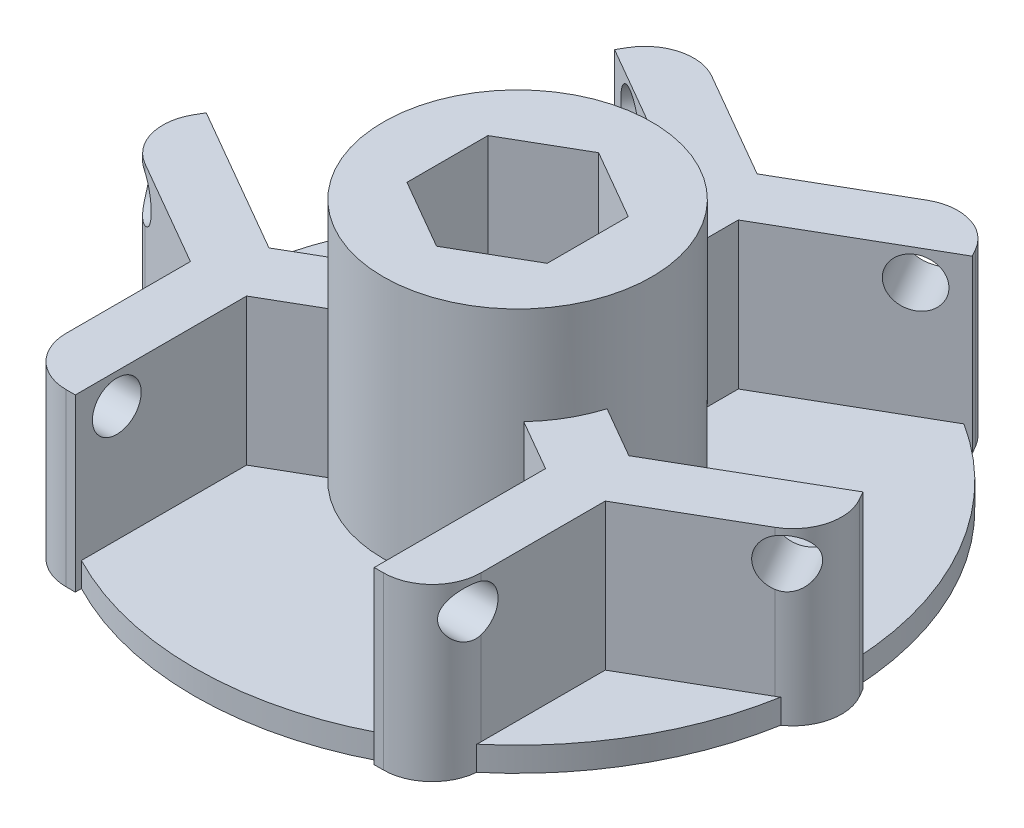
SolidWorks part; units mm, degrees
ref_plane "Alzado" through (0, 0, 0) normal (0, 0, 1) x (1, 0, 0)
ref_plane "Planta" through (0, 0, 0) normal (0, 1, 0) x (1, 0, 0)
ref_plane "Vista lateral" through (0, 0, 0) normal (1, 0, 0) x (0, 0, -1)
sketch "Croquis2" plane through (0, 0, 0) normal (0, 1, 0) x (1, 0, 0)
  circle A0 centre (0, 0) radius 26.5
  dimension "D1" = 53
extrude "Saliente-Extruir1" add sketch "Croquis2" along normal blind 2 and the other way blind 2
sketch "Croquis3" plane through (0, 0, 0) normal (0, 1, 0) x (1, 0, 0)
  line L1 (0, 6.6395) -> (-5.75, 3.3198)
  line L2 (-5.75, 3.3198) -> (-5.75, -3.3198)
  line L3 (-5.75, -3.3198) -> (0, -6.6395)
  line L4 (0, -6.6395) -> (5.75, -3.3198)
  line L5 (5.75, -3.3198) -> (5.75, 3.3198)
  line L6 (5.75, 3.3198) -> (0, 6.6395)
  circle A0 centre (0, 0) radius 11
  circle A1 centre (0, 0) radius 5.75 construction
  dimension "D1" = 22
  dimension "D2" = 11.5
extrude "Saliente-Extruir2" add sketch "Croquis3" along normal blind 22 and the other way blind 22
sketch "Croquis5" plane through (0, 0, 0) normal (0, 1, 0) x (1, 0, 0)
  line L0 (0, 0) -> (0, 3)
  line L2 (0, 0) -> (16.4545, -9.5)
  line L3 (0, 0) -> (-16.4545, -9.5)
  line L4 (-2.5, 8.395) -> (2.5, 8.395)
  line L6 (-2.5, 8.395) -> (-2.5, 19)
  line L7 (-2.5, 19) -> (2.5, 19)
  line L8 (2.5, 8.395) -> (2.5, 19)
  line L9 (8.5203, -2.0324) -> (17.7045, -7.3349)
  line L10 (17.7045, -7.3349) -> (15.2045, -11.6651)
  line L11 (6.0203, -6.3625) -> (15.2045, -11.6651)
  line L12 (8.5203, -2.0324) -> (6.0203, -6.3625)
  line L13 (-6.0203, -6.3625) -> (-15.2045, -11.6651)
  line L14 (-15.2045, -11.6651) -> (-17.7045, -7.3349)
  line L15 (-8.5203, -2.0324) -> (-17.7045, -7.3349)
  line L16 (-6.0203, -6.3625) -> (-8.5203, -2.0324)
  circle A0 centre (0, 0) radius 11 construction
  point P5 (0, 11)
  point P23 (0, 0)
  dimension "D1" = 120
  dimension "D2" = 120
  dimension "D3" = 19
  dimension "D4" = 19
  dimension "D5" = 3
  dimension "D6" = 5
extrude "Saliente-Extruir3" add sketch "Croquis5" along normal blind 14 contours L11 L10 L9 L12 | L13 L14 L15 L16 | L6 L7 L8 L4
sketch "Croquis6" plane through (0, 0, 0) normal (0, 1, 0) x (1, 0, 0)
  line L0 (0, -24.2) -> (0, 24.2) construction
  line L2 (-12.25, -11) -> (-12.25, -24)
  line L4 (12.25, -11) -> (12.25, -24)
  line L5 (12.25, -24) -> (13, -24)
  line L6 (-1.6692, 15.1088) -> (0.7058, 19.2224)
  line L7 (12.25, -23.4987) -> (12.25, -17.4531)
  line L8 (-12.25, -11) -> (-12.25, -9)
  line L9 (-13, -24) -> (-12.25, -24)
  line L10 (-17, -20) -> (-17, -9)
  line L12 (17, -20) -> (17, -9)
  line L13 (-12.25, -9) -> (-17, -9)
  line L14 (12.25, -11) -> (12.25, -9)
  line L15 (12.25, -9) -> (17, -9)
  line L16 (-8.8205, 24.7224) -> (0.7058, 19.2224)
  line L17 (-14.2846, 23.2583) -> (-14.6596, 22.6088)
  line L18 (-3.4013, 16.1088) -> (-14.6596, 22.6088)
  line L19 (-3.4013, 16.1088) -> (-1.6692, 15.1088)
  line L20 (-15.6513, -5.1088) -> (-26.9096, 1.3912)
  line L21 (-26.9096, 1.3912) -> (-27.2846, 0.7417)
  line L22 (-25.8205, -4.7224) -> (-16.2942, -10.2224)
  line L23 (-13.9192, -6.1088) -> (-16.2942, -10.2224)
  line L24 (-15.6513, -5.1088) -> (-13.9192, -6.1088)
  line L25 (13.9192, -6.1088) -> (16.2942, -10.2224)
  line L26 (25.8205, -4.7224) -> (16.2942, -10.2224)
  line L27 (27.2846, 0.7417) -> (26.9096, 1.3912)
  line L28 (15.6513, -5.1088) -> (26.9096, 1.3912)
  line L29 (15.6513, -5.1088) -> (13.9192, -6.1088)
  line L30 (3.4013, 16.1088) -> (14.6596, 22.6088)
  line L31 (14.6596, 22.6088) -> (14.2846, 23.2583)
  line L32 (8.8205, 24.7224) -> (-0.7058, 19.2224)
  line L33 (1.6692, 15.1088) -> (-0.7058, 19.2224)
  line L34 (3.4013, 16.1088) -> (1.6692, 15.1088)
  arc A0 (-14.2846, 23.2583) -> (-8.8205, 24.7224) centre (-10.8205, 21.2583) cw
  arc A1 (-27.2846, 0.7417) -> (-25.8205, -4.7224) centre (-23.8205, -1.2583) ccw
  circle A2 centre (0, 0) radius 26.5 construction
  arc A3 (13, -24) -> (17, -20) centre (13, -20) ccw
  arc A4 (-13, -24) -> (-17, -20) centre (-13, -20) cw
  arc A5 (27.2846, 0.7417) -> (25.8205, -4.7224) centre (23.8205, -1.2583) cw
  arc A6 (14.2846, 23.2583) -> (8.8205, 24.7224) centre (10.8205, 21.2583) ccw
  point P21 (17, -24)
  point P24 (-17, -24)
  point P53 (0, 0)
  dimension "D9" = 4
  dimension "D1" = 24.5
  dimension "D2" = 3
  dimension "D3" = 12.25
  dimension "D5" = 34
  dimension "D6" = 17
extrude "Saliente-Extruir5" add sketch "Croquis6" along normal blind 14 contours L2 L9 A4 L10 L13 L8 | L4 L5 A3 L12 L15 L14 | L20 L21 A1 L22 L23 L24 | L6 L16 A0 L17 L18 L19 | L30 L31 A6 L32 L33 L34 | L25 L26 A5 L27 L28 L29
sketch "Croquis7" plane through (0, 0, 0) normal (0, 1, 0) x (1, 0, 0)
  line L0 (12.25, -23.4987) -> (12.25, -9.9593) construction
  line L1 (-12.25, -30.1) -> (12.25, -30.1)
  line L2 (-12.25, -30.1) -> (-12.25, -11.1)
  line L3 (-12.25, -11.1) -> (12.25, -11.1)
  line L4 (12.25, -30.1) -> (12.25, -11.1)
  line L5 (-24.2, 0) -> (24.2, 0) construction
  dimension "D1" = 19
  dimension "D2" = 30.1
  dimension "D3" = 24.5
extrude "Saliente-Extruir12" add sketch "Croquis7" along normal blind 21
sketch "Croquis8" plane through (12.25, 0, 0) normal (1, 0, 0) x (0, 0, -1)
  line L0 (-30.1, 21) -> (-11.1, 21) construction
  line L1 (-30.1, 21) -> (-30.1, 0) construction
  circle A0 centre (-20.6, 11.5) radius 2
  dimension "D3" = 4
  dimension "D1" = 9.5
  dimension "D2" = 9.5
extrude "Cortar-Extruir1" cut sketch "Croquis8" against normal blind 37 and the other way blind 37
sketch "Croquis10" plane through (0, 21, 0) normal (0, 1, 0) x (1, 0, 0)
  line L1 (-12.25, -11.1) -> (12.25, -11.1)
  line L2 (-12.25, -11.1) -> (-12.25, -30.1)
  line L3 (-12.25, -30.1) -> (12.25, -30.1)
  line L4 (12.25, -11.1) -> (12.25, -30.1)
extrude "Cortar-Extruir2" cut sketch "Croquis10" against normal blind 19
ref_axis "Eje2" through (0, -24.2, 0) along (0, 1, 0)
pattern_circular "MatrizC2" count 3 over 360 about axis through (0, -24.2, 0) along (0, 1, 0) of "Cortar-Extruir1"
sketch "Croquis14" plane through (0, 2, 0) normal (0, 1, 0) x (1, 0, 0)
  line L0 (-12.25, -30.1) -> (-12.25, -23.4987)
  line L1 (-12.25, -23.4987) -> (-12.25, -30.1)
  line L2 (-12.25, -30.1) -> (12.25, -30.1)
  line L3 (12.25, -30.1) -> (12.25, -23.4987)
  arc A0 (-12.25, -23.4987) -> (12.25, -23.4987) centre (0, 0) ccw
  line M1 (-12.25, -9.9593) -> (-12.25, -24)
  line M2 (-12.25, -24) -> (-12.25, -30.1)
  line M3 (-12.25, -30.1) -> (12.25, -30.1)
  line M4 (12.25, -30.1) -> (12.25, -24)
  line M5 (12.25, -24) -> (12.25, -9.9593)
extrude "Cortar-Extruir3" cut sketch "Croquis14" against normal blind 19 contours A0 M1 M2 M3 M4 M5 region at (0, 2, 27.7258)
ref_axis "Eje3" through (-30.6026, 0, 0) along (1, 0, 0)
ref_axis "Eje4" through (0, 0, -29.15) along (0, 0, 1)
sketch "Croquis15" plane through (0, 0, 0) normal (0, 0, 1) x (1, 0, 0)
  line L0 (29.15, 0) -> (-29.15, 0) construction
  line L1 (-30.2326, 0) -> (28.9, 0)
  line L2 (-30.2326, 0) -> (-30.2326, -24.236)
  line L3 (-30.2326, -24.236) -> (28.9, -24.236)
  line L4 (28.9, 0) -> (28.9, -24.236)
  line L5 (-30.6026, 0) -> (30.6026, 0) construction
extrude "Cortar-Extruir5" cut sketch "Croquis15" against normal blind 33 and the other way blind 33
sketch "Croquis16" plane through (0, 2, 0) normal (0, 1, 0) x (1, 0, 0)
  circle A0 centre (0, 0) radius 0.5
  dimension "D1" = 1
extrude "Cortar-Extruir6" cut sketch "Croquis16" against normal blind 10
sketch "Croquis17" plane through (0, 0, 0) normal (0, -1, 0) x (1, 0, 0)
  line L0 (0, 0) -> (1.0227, 0)
  line L1 (12.1, 0) -> (-12.1, 0) construction
  line L3 (-1.0752, -0.5) -> (1.0752, -0.5)
  line L4 (-1.0752, -0.5) -> (-1.0752, 0.5)
  line L5 (-1.0752, 0.5) -> (1.0752, 0.5)
  line L6 (1.0752, -0.5) -> (1.0752, 0.5)
  line L7 (-1.0752, -0.5) -> (1.0752, 0.5) construction
  line L8 (-1.0752, 0.5) -> (1.0752, -0.5) construction
  line L9 (0.5, -0.8236) -> (-0.5, -0.8236)
  line L10 (0.5, -0.8236) -> (0.5, 0.8236)
  line L11 (0.5, 0.8236) -> (-0.5, 0.8236)
  line L12 (-0.5, -0.8236) -> (-0.5, 0.8236)
  line L13 (0.5, -0.8236) -> (-0.5, 0.8236) construction
  line L14 (0.5, 0.8236) -> (-0.5, -0.8236) construction
  circle M3 centre (0, 0) radius 0.5
  dimension "D1" = 1
  dimension "D2" = 1
extrude "Cortar-Extruir8" cut sketch "Croquis17" against normal blind 0.1 contours L3 L12 L5 L4 | L12 L5 L10 L11 | L10 L3 L6 L5 | L12 L9 L10 L3 | L3 L10 M3 | L12 L3 M3 | L12 L5 M3 | L10 L5 M3 region at (-0.7876, 0, 0) region at (-0.3883, 0, -0.3883) region at (0, 0, -0.6618) region at (0.3883, 0, -0.3883) region at (-0.3883, 0, 0.3883) region at (0, 0, 0.6618) region at (0.5115, 0, -0.25) region at (0.3883, 0, 0.3883)
